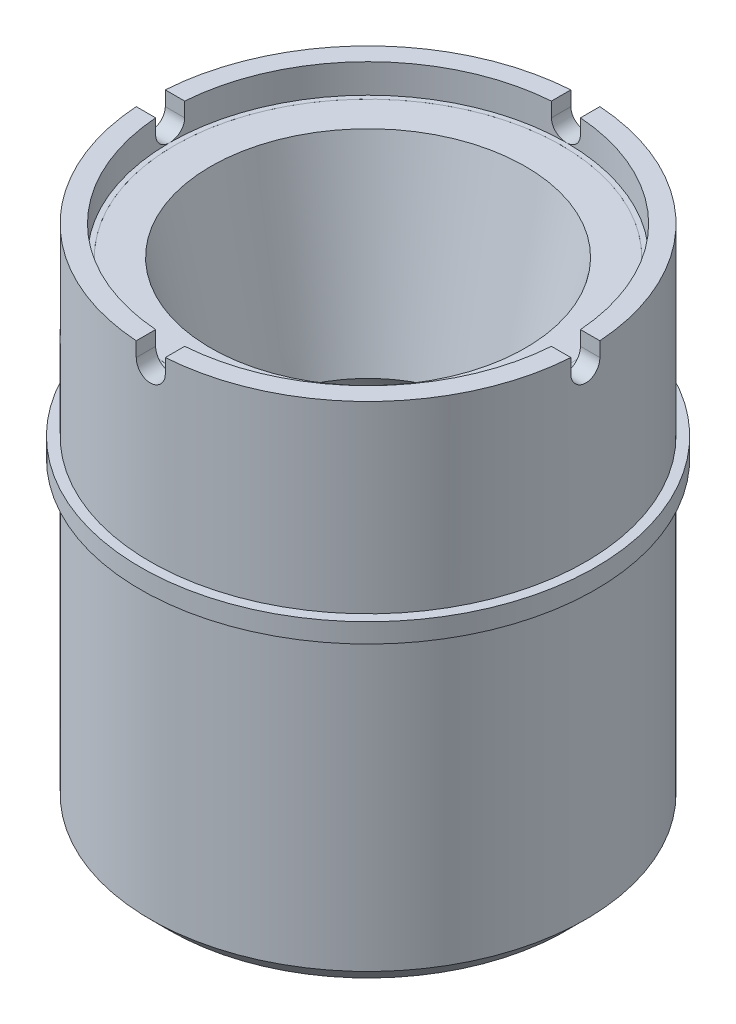
SolidWorks part; units mm, degrees
note: '?' marks a value the reader was unsure of.
other "球壳" parameters "D1"=81.3186, "D2"=14.2181, "D3"=3.8444, "D4"=46, "D5"=11.364, "D6"=4.1959, "D7"=3.7916, "D8"=4.4493, "D9"=3.4003, "D10"=2, "D11"=15.2084, "D12"=9.9715, "D13"=4.0911
ref_plane "前视基准面" through (0, 0, 0) normal (0, 0, 1) x (1, 0, 0)
ref_plane "上视基准面" through (0, 0, 0) normal (0, 1, 0) x (1, 0, 0)
ref_plane "右视基准面" through (0, 0, 0) normal (1, 0, 0) x (0, 0, -1)
other "Configuration Table"
sketch "草图1" plane through (0, 0, 0) normal (0, 0, 1) x (1, 0, 0)
  line L0 (0, 0) -> (0, 17.6209) construction
  line L1 (0, 0) -> (22.5, 0)
  line L2 (22.5, 0) -> (22.5, 50)
  line L3 (22.5, 50) -> (20, 50)
  line L4 (20, 50) -> (20, 48)
  line L5 (20, 48) -> (19, 48)
  line L6 (19, 48) -> (19, 4)
  line L7 (19, 4) -> (0, 4)
  line L8 (0, 4) -> (0, 0)
  line L10 (19, 4) -> (18, 4)
  line L11 (19, 4) -> (19, 6)
  line L12 (19, 6) -> (18, 6)
  line L13 (18, 4) -> (18, 6)
  line L14 (22.5, 32) -> (23.5, 32)
  line L15 (22.5, 32) -> (22.5, 34)
  line L16 (22.5, 34) -> (23.5, 34)
  line L17 (23.5, 32) -> (23.5, 34)
  line L18 (22.5, 50) -> (20.5, 50)
  line L19 (22.5, 50) -> (22.5, 53)
  line L20 (22.5, 53) -> (20.5, 53)
  line L21 (20.5, 50) -> (20.5, 53)
  dimension "D1" = 4
  dimension "D4" = 19
  dimension "D5" = 22.5
  dimension "D2" = 2
  dimension "D3" = 50
  dimension "D6" = 18
  dimension "D7" = 2
  dimension "D8" = 32
  dimension "D9" = 2
  dimension "D10" = 23.5
  dimension "D11" = 20
  dimension "D12" = 2
  dimension "D13" = 3
revolve "旋转" add sketch "草图1" angle 360 about L0
sketch "草图2" plane through (0, 0, 0) normal (0, 0, 1) x (1, 0, 0)
  line L0 (19, 48) -> (19, 4) construction
  line L1 (19, 6) -> (18, 6) construction
  line L2 (18, 4) -> (18, 6) construction
  line L3 (19, 4) -> (0, 4) construction
  line L4 (19, 48) -> (19, 4)
  line L5 (19, 6) -> (18, 6)
  line L6 (18, 4) -> (18, 6)
  line L7 (19, 4) -> (0, 4)
  line L9 (0, 0) -> (0, 64.7268) construction
  line L10 (0, 11) -> (0, 4)
  line L11 (20, 48) -> (19, 48) construction
  line L12 (20, 50) -> (20, 48) construction
  line L13 (20, 48) -> (19, 48)
  line L14 (20, 50) -> (20, 48)
  line L15 (20, 50) -> (0, 50)
  line L16 (0, 50) -> (0, 11)
  line L17 (19, 38) -> (0, 38)
  line L18 (12.5, 24.5) -> (19, 24.5)
  line L19 (19, 38) -> (12.5, 38)
  line L20 (19, 38) -> (19, 13)
  arc A0 (0, 11) -> (0, 38) centre (0, 24.5) ccw
  dimension "D2" = 13.5
  dimension "D1" = 12
revolve "下球座" add sketch "草图2" angle 360 about L9
sketch "草图3" plane through (0, 0, 0) normal (0, 0, 1) x (1, 0, 0)
  line L0 (0, 24.5) -> (6.8327, 50) construction
  line L1 (20, 50) -> (0, 50) construction
  line L2 (0, 50) -> (0, 11) construction
  line L3 (20, 48) -> (19, 48) construction
  line L4 (19, 48) -> (19, 4) construction
  line L5 (20, 50) -> (20, 48) construction
  line L6 (20, 48) -> (19, 48)
  line L7 (19, 48) -> (19, 4)
  line L8 (20, 50) -> (20, 48)
  line L9 (20, 50) -> (0, 50)
  line L10 (0, 50) -> (0, 11)
  line L11 (12.5, 24.5) -> (19, 24.5) construction
  line L12 (12.0065, 30.672) -> (16.2571, 50)
  line L13 (12.5, 24.5) -> (19, 24.5)
  arc A0 (0, 11) -> (0, 38) centre (0, 24.5) ccw construction
  arc A1 (0, 11) -> (0, 38) centre (0, 24.5) ccw
  dimension "D1" = 15
  dimension "D2" = 10
  dimension "D3" = 2.597
revolve "上球座" add sketch "草图3" angle 360 about L10
sketch "草图4" plane through (0, 0, 0) normal (0, 0, 1) x (1, 0, 0)
  line L0 (0, 53) -> (0, 0) construction
  line L1 (22.5, 53) -> (-22.5, 53) construction
  line L3 (-1.5, 53) -> (1.5, 53)
  line L4 (-1.5, 53) -> (-1.5, 51.5)
  line L6 (1.5, 53) -> (1.5, 51.5)
  line L7 (16.2571, 50) -> (-16.2571, 50) construction
  line L8 (16.2571, 50) -> (-16.2571, 50)
  arc A0 (-1.5, 51.5) -> (1.5, 51.5) centre (0, 51.5) ccw
  dimension "D1" = 3
extrude "切除-拉伸1" cut sketch "草图4" against normal up to next contours L0 L3 L4 A0 | L3 L0 A0 L6
ref_axis "基准轴1" through (0, 32, 0) along (0, -1, 0)?
pattern_circular "阵列(圆周)1" count 4 over 360 about axis through (0, 0, 0) along (0, 1, 0) of "切除-拉伸1"
chamfer "倒角1" distance 2 angle 45 1 edges at (0, 0, -22.5)
sketch "草图5" plane through (0, 53, 0) normal (0, 1, 0) x (1, 0, 0)
  circle A0 centre (0, 0) radius 20.5
  circle A1 centre (0, 0) radius 22.5
extrude "切除-拉伸2" [suppressed] cut sketch "草图5" against normal offset from surface (1 mm away) 2
equation "\"壳体外径\"= 45"
equation "\"壳体总高\"= 50"
equation "\"壳体内孔\"= 38"
equation "\"收口端内孔\"= 41"
equation "\"底部封闭端厚\"= 4"
equation "\"定位台阶内径\"= 36"
equation "\"定位台阶高\"= 2"
equation "\"压装段长\"= 32"
equation "\"收口翻边宽\"= 3"
equation "\"球头直径\"= 27"
equation "\"上球座法兰外径\"= 40"
equation "\"上球座法兰厚\"= 2"
equation "\"上球座高\"= 12"
equation "\"防尘罩下卡径\"= 44"
equation "\"防尘罩上卡径\"= 16"
equation "\"防尘罩自由高\"= 28"
equation "\"球销杆部直径\"= 15"
equation "\"收口端壁厚\"= (\"壳体外径\" - \"收口端内孔\") / 2"
equation "\"D1@草图1\"=\"底部封闭端厚\""
equation "\"D4@草图1\"=\"壳体内孔\"/2"
equation "\"D5@草图1\"=\"壳体外径\"/2"
equation "\"D2@草图1\"=\"上球座法兰厚\""
equation "\"D3@草图1\"=\"壳体总高\""
equation "\"D6@草图1\"=\"定位台阶内径\"/2"
equation "\"D7@草图1\"=\"定位台阶高\""
equation "\"D8@草图1\"=\"压装段长\""
equation "\"D9@草图1\"=\"压装段法兰厚\""
equation "\"压装段法兰厚\"= 2"
equation "\"压装段法兰外径\"= \"壳体外径\" + 2"
equation "\"D10@草图1\"=\"压装段法兰外径\"/2"
equation "\"D11@草图1\"=\"上球座法兰外径\"/2"
equation "\"D12@草图1\"=\"收口端壁厚\""
equation "\"D13@草图1\"=\"收口翻边宽\""
equation "\"D1@草图2\"=\"上球座高\""
equation "\"D2@草图2\"=\"球头直径\"/2"
equation "\"单平面球铰行程\"= 30"
equation "\"D1@草图3\"=\"单平面球铰行程\"/2"
equation "\"锥面大端直径\"= 20"
equation "\"锥度比\"= 11"
equation "\"锥度\"= atn(1 / \"锥度比\")"
equation "\"D2@草图3\"=\"锥面大端直径\"/2"
equation "\"D3@草图3\"=\"锥度\"/2"
equation "\"D1@切除-拉伸2\"=\"收口端壁厚\""
